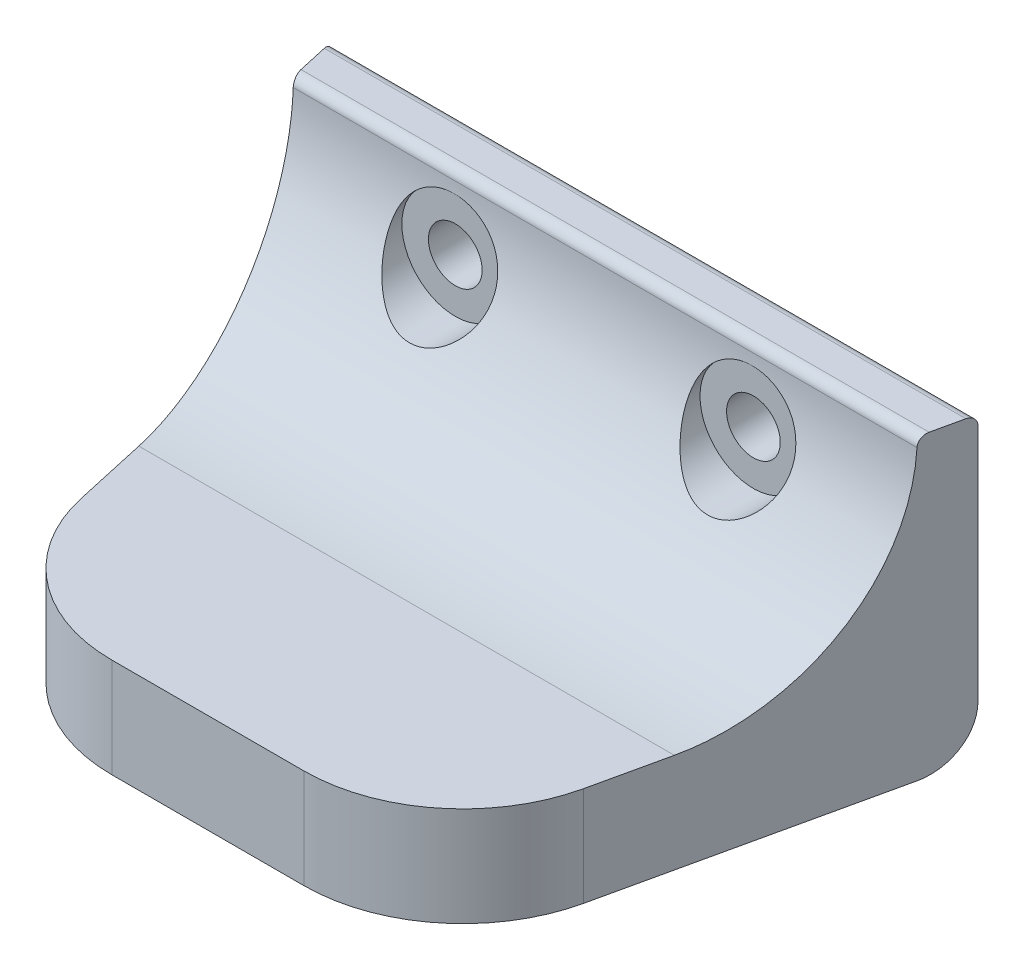
SolidWorks part; units mm, degrees
ref_plane "Front Plane" through (0, 0, 0) normal (0, 0, 1) x (1, 0, 0)
ref_plane "Top Plane" through (0, 0, 0) normal (0, 1, 0) x (1, 0, 0)
ref_plane "Right Plane" through (0, 0, 0) normal (1, 0, 0) x (0, 0, -1)
sketch "Sketch1" plane through (0, 0, 0) normal (0, 1, 0) x (1, 0, 0)
  line L0 (-41.275, 28.575) -> (-28.575, -28.575)
  line L1 (-41.275, -28.575) -> (41.275, -28.575) construction
  line L2 (-41.275, -28.575) -> (-41.275, 28.575) construction
  line L3 (-41.275, 28.575) -> (41.275, 28.575) construction
  line L4 (41.275, -28.575) -> (41.275, 28.575) construction
  line L5 (-41.275, -28.575) -> (41.275, 28.575) construction
  line L6 (-41.275, 28.575) -> (41.275, -28.575) construction
  line L7 (-28.575, -28.575) -> (28.575, -28.575)
  line L8 (28.575, -28.575) -> (41.275, 28.575)
  line L9 (0, 28.575) -> (0, -28.575) construction
  line L10 (-41.275, 28.575) -> (41.275, 28.575)
  line L11 (-39.8639, 22.225) -> (39.8639, 22.225)
  point P0 (0, 0)
  dimension "D1" = 82.55
  dimension "D2" = 57.15
  dimension "D3" = 57.15
  dimension "D4" = 6.35
extrude "Boss-Extrude1" add sketch "Sketch1" along normal blind 12.7 contours L11 L0 L7 L8 | L0 L11 L8 L10 region at (0, 0, -25.4184) region at (0, 0, 1.7784)
extrude "Boss-Extrude2" add sketch "Sketch1<5>" along normal blind 38.1 contours L0 L11 L8 L10 region at (0, 0, -25.4184)
sketch "Sketch1<5>" plane through (0, 0, 0) normal (0, 1, 0) x (1, 0, 0) same geometry as "Sketch1"
fillet "Fillet1" radius 25.4 1 edges at (0, 12.7, -22.225)
fillet "Fillet2" radius 20.32 2 edges at (28.575, 6.35, 28.575) (-28.575, 6.35, 28.575)
fillet "Fillet3" radius 6.35 1 edges at (0, 0, -28.575)
sketch "Sketch3" plane through (0, 0, -28.575) normal (0, 0, -1) x (-1, 0, 0)
  line L0 (41.275, 22.225) -> (-41.275, 22.225) construction
  line L1 (41.275, 38.1) -> (41.275, 6.35) construction
  line L2 (-41.275, 38.1) -> (-41.275, 6.35) construction
fillet "Fillet4" radius 1.27 2 edges at (0, 38.1, -22.225) (0, 38.1, -28.575)
sketch "Sketch4" plane through (0, 0, -28.575) normal (0, 0, -1) x (-1, 0, 0)
  line L0 (41.275, 28.7031) -> (-41.275, 28.7031) construction
  line L4 (41.275, 6.35) -> (41.275, 36.83)
  line L5 (41.275, 36.83) -> (-41.275, 36.83)
  line L6 (-41.275, 36.83) -> (-41.275, 6.35)
  line L7 (-41.275, 6.35) -> (41.275, 6.35)
  line L8 (41.275, 6.35) -> (41.275, 36.83)
  line L9 (41.275, 36.83) -> (-41.275, 36.83)
  line L10 (-41.275, 36.83) -> (-41.275, 6.35)
  line L11 (-41.275, 6.35) -> (41.275, 6.35)
  circle A0 centre (19.177, 28.7031) radius 3.429
  circle A2 centre (-18.923, 28.7031) radius 3.429
  circle A3 centre (-18.923, 28.7031) radius 5.5563
  circle A5 centre (19.177, 28.7031) radius 5.5563
  dimension "D2" = 6.858
  dimension "D3" = 2.1273
  dimension "D1" = 0
extrude "Cut-Extrude1" cut sketch "Sketch4" against normal blind 38.1 contours A2 L0 | L0 A2 | L0 A0 | A0 L0 region at (-19.177, 27.2478, -28.575) region at (-19.177, 30.1584, -28.575) region at (18.923, 27.2478, -28.575) region at (18.923, 30.1584, -28.575)
ref_plane "Plane1" through (0, 0, -22.225) normal (0, 0, -1) x (-1, 0, 0)
sketch "Sketch5" plane through (0, 0, -22.225) normal (0, 0, -1) x (-1, 0, 0)
  circle A0 centre (-18.923, 28.7031) radius 6.8262
  circle A2 centre (19.177, 28.7031) radius 6.8263
  circle A3 centre (-18.923, 28.7031) radius 3.429 construction
  circle A5 centre (19.177, 28.7031) radius 3.429 construction
  dimension "D1" = 13.6525
extrude "Cut-Extrude4" cut sketch "Sketch5" against normal blind 20.32
